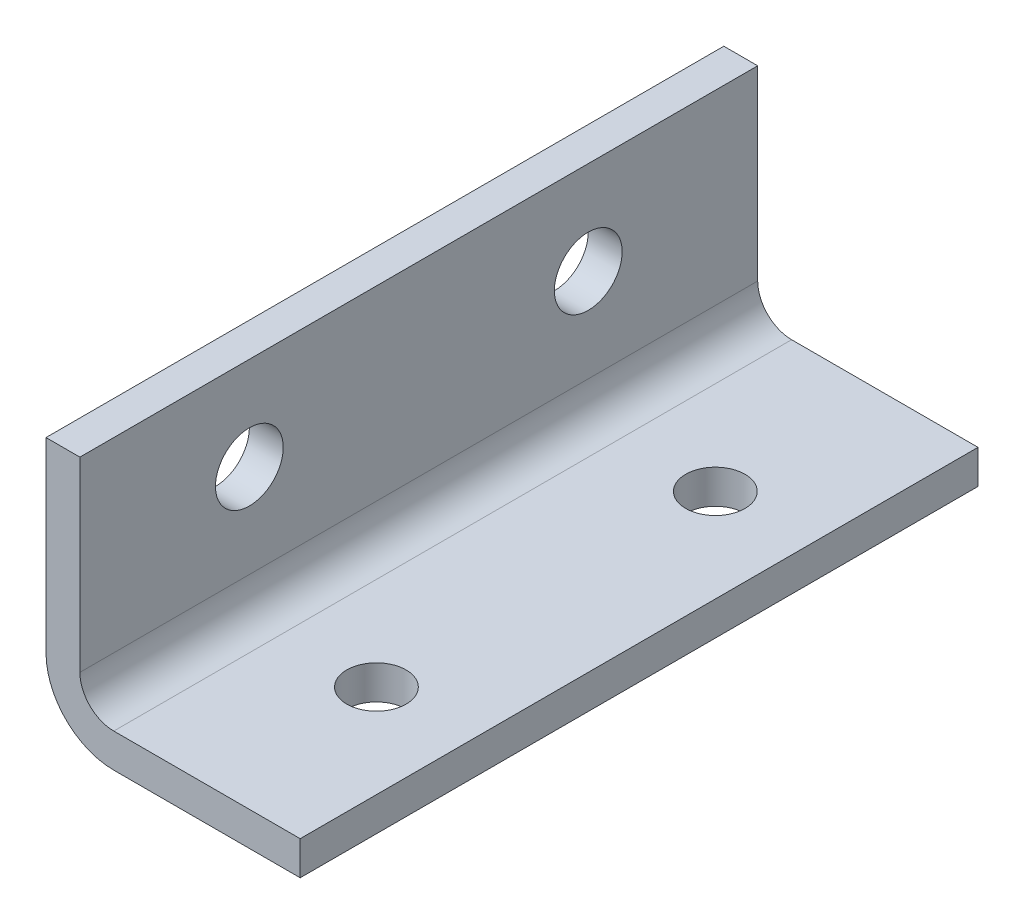
SolidWorks part; units mm, degrees
ref_plane "Front Plane" through (0, 0, 0) normal (0, 0, 1) x (1, 0, 0)
ref_plane "Top Plane" through (0, 0, 0) normal (0, 1, 0) x (1, 0, 0)
ref_plane "Right Plane" through (0, 0, 0) normal (1, 0, 0) x (0, 0, -1)
sketch "Sketch1" plane through (0, 0, 0) normal (0, 0, 1) x (1, 0, 0)
  line L0 (0, 4) -> (0, 15)
  line L1 (0, 15) -> (2, 15)
  line L2 (2, 15) -> (2, 4)
  line L3 (4, 2) -> (15, 2)
  line L4 (15, 2) -> (15, 0)
  line L5 (15, 0) -> (4, 0)
  arc A0 (2, 4) -> (4, 2) centre (4, 4) ccw
  arc A1 (0, 4) -> (4, 0) centre (4, 4) ccw
  point P11 (0, 0)
  dimension "D5" = 2
  dimension "D6" = 4
  dimension "D1" = 15
  dimension "D2" = 15
  dimension "D3" = 2
  dimension "D4" = 2
extrude "Boss-Extrude1" add sketch "Sketch1" along normal mid plane 40
sketch "Sketch2" plane through (2, 0, 0) normal (1, 0, 0) x (0, 0, -1)
  line L0 (-20, 4) -> (-20, 15) construction
  line L1 (0, 0) -> (0, 15) construction
  line L2 (-20, 15) -> (20, 15) construction
  circle A0 centre (-10, 9.5) radius 2
  circle A2 centre (10, 9.5) radius 2
  point P7 (-20, 9.5)
  point P12 (0, 0)
  dimension "D1" = 4
  dimension "D2" = 10
extrude "Cut-Extrude1" cut sketch "Sketch2" against normal through all
sketch "Sketch3" plane through (0, 2, 0) normal (0, 1, 0) x (1, 0, 0)
  line L0 (0, 0) -> (15, 0) construction
  line L1 (15, -20) -> (15, 20) construction
  line L2 (15, -20) -> (4, -20) construction
  circle A0 centre (9.5, -10) radius 1.75
  circle A1 centre (9.5, 10) radius 1.75
  point P9 (9.5, -20)
  dimension "D2" = 3.5
  dimension "D1" = 10
extrude "Cut-Extrude2" cut sketch "Sketch3" against normal through all
